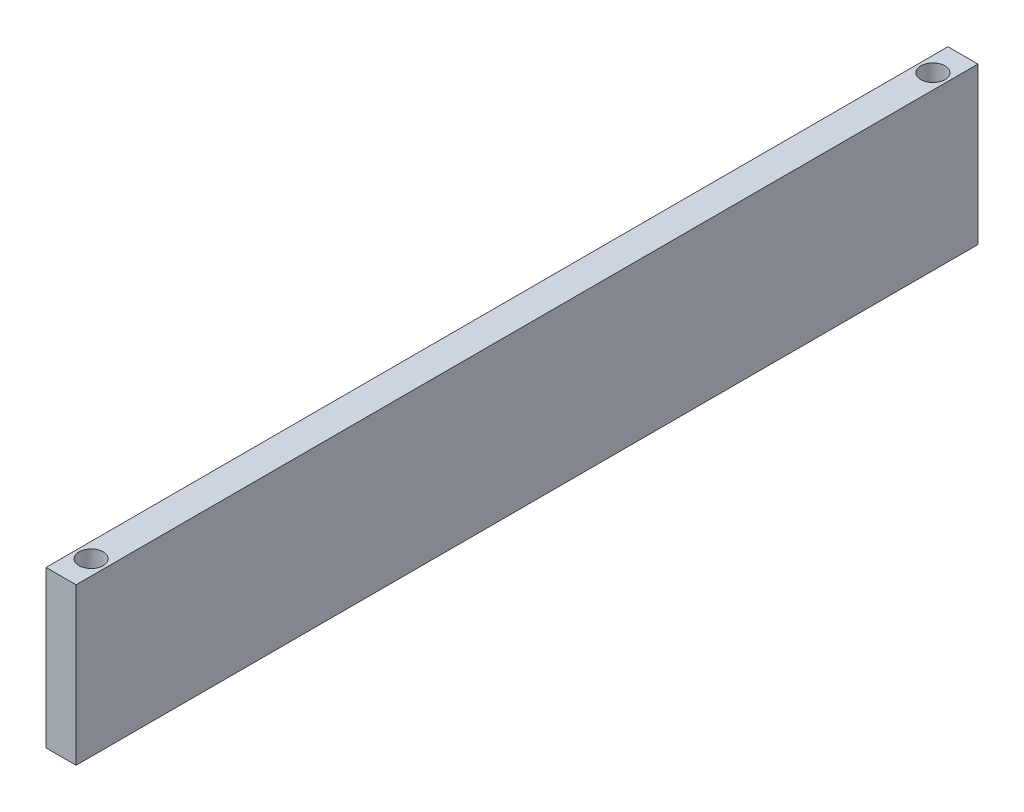
SolidWorks part; units mm, degrees
other "Markup1"
sketch "Sketch6" plane through (0, 0, 0) normal (0.7258, -0.6292, 0.2781) x (-0.261, -0.6259, -0.735)
ref_plane "Front Plane" through (0, 0, 0) normal (0, 0, 1) x (1, 0, 0)
ref_plane "Top Plane" through (0, 0, 0) normal (0, 1, 0) x (1, 0, 0)
ref_plane "Right Plane" through (0, 0, 0) normal (1, 0, 0) x (0, 0, -1)
sketch "Sketch1" plane through (0, 0, 0) normal (0, 0, 1) x (1, 0, 0)
  line L1 (-6.35, 0) -> (-6.35, 33.02)
  line L2 (-6.35, 33.02) -> (0, 33.02)
  line L3 (0, 33.02) -> (0, 0)
  line L6 (-6.35, 0) -> (0, 0)
  dimension "D3" = 6.35
  dimension "D4" = 33.02
extrude "Boss-Extrude1" add sketch "Sketch1" against normal blind 190.5
sketch "Sketch2" plane through (-6.35, 0, 0) normal (-1, 0, 0) x (0, 0, 1)
  line L0 (-190.5, 33.02) -> (-190.5, 0) construction
  circle A1 centre (-160.5, 16.51) radius 3.175
  point P5 (-190.5, 16.51)
  dimension "D1" = 6.35
  dimension "D2" = 30
extrude "Cut-Extrude1" [suppressed] cut sketch "Sketch2" against normal up to next
sketch "Sketch3" plane through (0, 33.02, 0) normal (0, 1, 0) x (1, 0, 0)
  line L0 (-3.175, 190.5) -> (-3.175, 0) construction
  line L1 (0, 190.5) -> (-6.35, 190.5) construction
  line L2 (0, 0) -> (-6.35, 0) construction
  circle A0 centre (-3.175, 6.35) radius 2.54
  circle A1 centre (-3.175, 184.15) radius 2.54
  dimension "D1" = 5.08
  dimension "D3" = 6.35
  dimension "D2" = 6.35
extrude "Cut-Extrude2" cut sketch "Sketch3" against normal through all
sketch "Sketch4" plane through (0, 0, 0) normal (0, -1, 0) x (1, 0, 0)
  line L0 (-9.525, 0) -> (-9.525, -381) construction
  line L1 (-12.7, 0) -> (0, 0) construction
  line L2 (-12.7, -381) -> (0, -381) construction
  line L3 (0, -381) -> (0, 0) construction
  circle A0 centre (-9.525, -374.65) radius 2.54
  circle A1 centre (-9.525, -6.35) radius 2.54
  dimension "D2" = 5.08
  dimension "D1" = 9.525
  dimension "D3" = 6.35
  dimension "D4" = 6.35
sketch "Sketch5" plane through (0, 0, -381) normal (0, 0, -1) x (-1, 0, 0)
  line L1 (6.35, 6.35) -> (0, 6.35)
  line L2 (6.35, 6.35) -> (6.35, 0)
  line L3 (6.35, 0) -> (0, 0)
  line L4 (0, 6.35) -> (0, 0)
